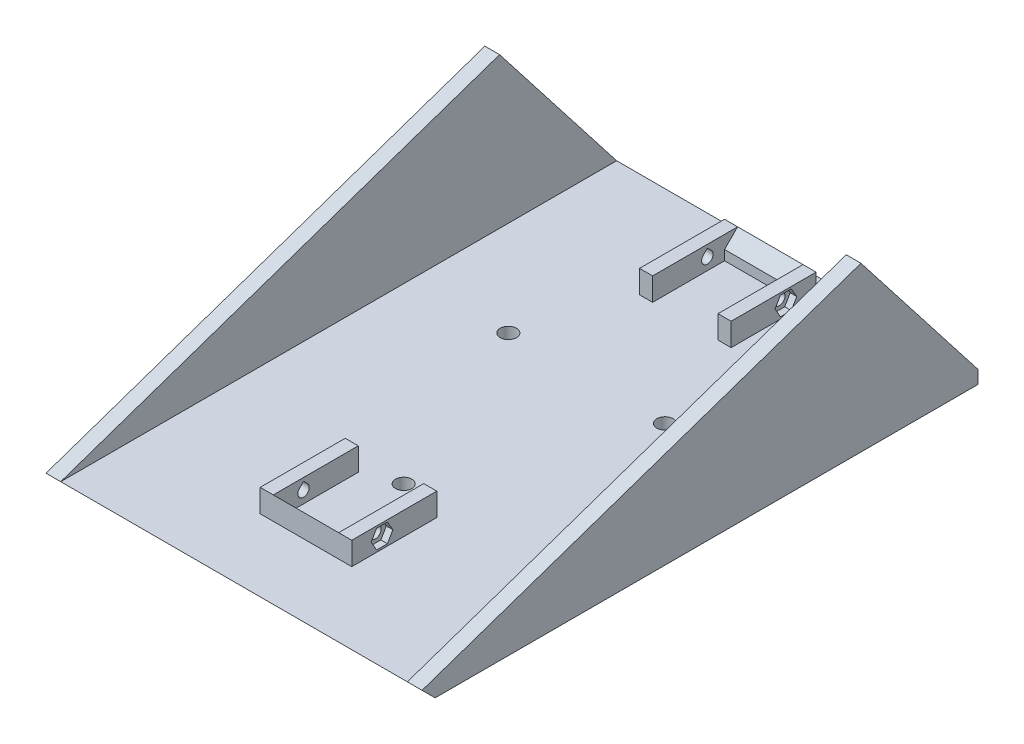
SolidWorks part; units mm, degrees
ref_plane "Front Plane" through (0, 0, 0) normal (0, 0, 1) x (1, 0, 0)
ref_plane "Top Plane" through (0, 0, 0) normal (0, 1, 0) x (1, 0, 0)
ref_plane "Right Plane" through (0, 0, 0) normal (1, 0, 0) x (0, 0, -1)
sketch "Sketch1" plane through (0, 0, 0) normal (0, 1, 0) x (1, 0, 0)
  line L1 (0, 0) -> (115, 0)
  line L2 (0, 0) -> (0, 170)
  line L3 (0, 170) -> (115, 170)
  line L4 (115, 0) -> (115, 170)
  line L5 (0, 170) -> (4.5, 170)
  line L6 (0, 170) -> (0, 0)
  line L7 (0, 0) -> (4.5, 0)
  line L8 (4.5, 170) -> (4.5, 0)
  dimension "D1" = 115
  dimension "D2" = 170
  dimension "D3" = 4.5
extrude "Boss-Extrude1" add sketch "Sketch1" along normal blind 4 contours L3 L8 L1 L4 | L8 L3 L2 L1 region at (2.25, 0, -85) region at (59.75, 0, -85)
extrude "Boss-Extrude2" add sketch "Sketch1<4>" along normal blind 50 contours L8 L3 L2 L1 region at (2.25, 0, -85)
sketch "Sketch1<4>" plane through (0, 0, 0) normal (0, 1, 0) x (1, 0, 0) same geometry as "Sketch1"
sketch "Sketch2" plane through (0, 0, 0) normal (-1, 0, 0) x (0, 0, 1)
  line L0 (-134.204, 50) -> (-170, 4)
  line L1 (0, 50) -> (-170, 50) construction
  line L2 (-170, 4) -> (-182.3926, 4)
  line L3 (-182.3926, 4) -> (-182.3926, 57.4026)
  line L4 (-182.3926, 57.4026) -> (5.7459, 57.4026)
  line L5 (5.7459, 57.4026) -> (5.7459, 4)
  line L6 (5.7459, 4) -> (0, 4)
  line L7 (0, 50) -> (0, 0) construction
  line L8 (0, 4) -> (-134.204, 50)
extrude "Cut-Extrude1" cut sketch "Sketch2" against normal up to surface (4.5 mm away) up to face at (4.5, 27, -85)
ref_axis "Axis1" through (57.5, 0, -170) along (0, 0, 1)
ref_plane "Plane1" through (57.5, 0, 0) normal (1, 0, 0) x (0, 0, -1)
mirror "Mirror1" about plane through (57.5, 0, 0) normal (1, 0, 0) of "Cut-Extrude1", "Boss-Extrude2"
sketch "Sketch3" plane through (0, 4, 0) normal (0, 1, 0) x (1, 0, 0)
  line L0 (4.5, 170) -> (110.5, 170) construction
  line L5 (57.5, 160) -> (47.5, 160)
  line L6 (47.5, 160) -> (47.5, 142)
  line L7 (57.5, 160) -> (57.5, 170) construction
  line L8 (4.5, 170) -> (110.5, 170) construction
  line L9 (110.5, 170) -> (110.5, 134.204) construction
  line L11 (57.5, 164) -> (43.5, 164)
  line L12 (43.5, 164) -> (43.5, 138)
  line L13 (43.5, 138) -> (47.5, 138)
  line L14 (57.5, 164) -> (57.5, 160)
  line L16 (47.5, 142) -> (47.5, 138)
  line L17 (43.5, 138) -> (57.5, 138) construction
  line L18 (47.5, 142) -> (57.5, 142) construction
  point P12 (57.5, 170)
  dimension "D1" = 10
  dimension "D2" = 106
  dimension "D3" = 10
  dimension "D5" = 26
  dimension "D4" = 4
extrude "Saliente-Extruir1" add sketch "Sketch3" along normal blind 7
sketch "Croquis1" plane through (0, 4, 0) normal (0, 1, 0) x (1, 0, 0)
  line L0 (47.5, 138) -> (47.5, 48) construction
  line L1 (47.5, 93) -> (18.6251, 93) construction
  line L2 (57.5, 26) -> (57.5, 22)
  line L3 (47.5, 26) -> (57.5, 26)
  line L4 (57.5, 22) -> (43.5, 22)
  line L5 (43.5, 22) -> (43.5, 48)
  line L6 (57.5, 160) -> (57.5, 164)
  line L7 (57.5, 164) -> (43.5, 164)
  line L8 (43.5, 164) -> (43.5, 138)
  line L9 (43.5, 138) -> (47.5, 138)
  line L10 (47.5, 138) -> (47.5, 160)
  line L11 (47.5, 160) -> (57.5, 160)
  line L12 (57.5, 160) -> (57.5, 164) construction
  line L13 (57.5, 164) -> (43.5, 164) construction
  line L14 (43.5, 164) -> (43.5, 138) construction
  line L15 (43.5, 138) -> (47.5, 138) construction
  line L16 (47.5, 138) -> (47.5, 160) construction
  line L17 (47.5, 160) -> (57.5, 160) construction
  line L18 (43.5, 48) -> (47.5, 48)
  line L19 (47.5, 48) -> (47.5, 26)
  dimension "D2" = 90
  dimension "D1" = 0
extrude "Saliente-Extruir2" add sketch "Croquis1" along normal blind 7
mirror "Simetría1" about plane through (57.5, 11, -164) normal (-1, 0, 0) of "Saliente-Extruir2", "Saliente-Extruir1"
sketch "Croquis2" plane through (47.5, 0, 0) normal (1, 0, 0) x (0, 0, -1)
  line L0 (48, 4) -> (138, 4) construction
  line L1 (93, 4) -> (93, 16.2134) construction
  line L2 (160, 7.5) -> (156.5, 7.5)
  line L3 (156.5, 7.5) -> (154.75, 7.5)
  line L4 (138, 4) -> (160, 4)
  line L5 (160, 4) -> (160, 11)
  line L6 (160, 11) -> (138, 11)
  line L7 (138, 11) -> (138, 4)
  line L8 (138, 4) -> (160, 4)
  line L9 (160, 4) -> (160, 11)
  line L10 (160, 11) -> (138, 11)
  line L11 (138, 11) -> (138, 4)
  line L12 (26, 4) -> (48, 4)
  line L13 (48, 4) -> (48, 11)
  line L14 (48, 11) -> (26, 11)
  line L15 (26, 11) -> (26, 4)
  line L16 (26, 4) -> (48, 4)
  line L17 (48, 4) -> (48, 11)
  line L18 (48, 11) -> (26, 11)
  line L19 (26, 11) -> (26, 4)
  line L20 (31.25, 9.9749) -> (32.4874, 8.7374)
  line L21 (154.75, 9.9749) -> (155.9874, 8.7374)
  line L22 (31.25, 9.9749) -> (30.0126, 8.7374)
  line L23 (154.75, 9.9749) -> (153.5126, 8.7374)
  arc A0 (153.5126, 8.7374) -> (155.9874, 8.7374) centre (154.75, 7.5) ccw
  arc A1 (32.4874, 8.7374) -> (30.0126, 8.7374) centre (31.25, 7.5) cw
  dimension "D3" = 3.5
  dimension "D4" = 1.75
  dimension "D1" = 0
  dimension "D2" = 0
extrude "Cortar-Extruir1" cut sketch "Croquis2" against normal blind 7 and the other way blind 31 contours A1 L20 L22 | A0 L21 L23 region at (47.5, 7.6229, -154.75) region at (47.5, 7.6229, -31.25)
sketch "Croquis4" plane through (71.5, 0, 0) normal (1, 0, 0) x (0, 0, -1)
  line L0 (154.75, 7.5) -> (154.75, 4) construction
  line L1 (158.0698, 7.5) -> (156.4099, 10.375)
  line L2 (156.4099, 10.375) -> (153.0901, 10.375)
  line L3 (153.0901, 10.375) -> (151.4302, 7.5)
  line L4 (151.4302, 7.5) -> (153.0901, 4.625)
  line L5 (153.0901, 4.625) -> (156.4099, 4.625)
  line L6 (156.4099, 4.625) -> (158.0698, 7.5)
  line L7 (164, 4) -> (138, 4) construction
  line L8 (48, 7.5) -> (138, 7.5) construction
  line L9 (48, 11) -> (48, 4) construction
  line L10 (138, 11) -> (138, 4) construction
  line L11 (93, 7.5) -> (93, 14.1152) construction
  line L18 (154.75, 7.5) -> (158.8346, 7.5) construction
  line L19 (29.5901, 4.625) -> (27.9302, 7.5)
  line L20 (32.9099, 4.625) -> (29.5901, 4.625)
  line L21 (34.5698, 7.5) -> (32.9099, 4.625)
  line L22 (32.9099, 10.375) -> (34.5698, 7.5)
  line L23 (29.5901, 10.375) -> (32.9099, 10.375)
  line L24 (27.9302, 7.5) -> (29.5901, 10.375)
  circle A0 centre (154.75, 7.5) radius 2.875 construction
  arc A1 (153.5126, 8.7374) -> (155.9874, 8.7374) centre (154.75, 7.5) ccw construction
  arc M13 (155.9874, 8.7374) -> (153.5126, 8.7374) centre (154.75, 7.5) cw
  line M14 (153.5126, 8.7374) -> (154.75, 9.9749)
  line M15 (154.75, 9.9749) -> (155.9874, 8.7374)
  dimension "D1" = 5.75
extrude "Cortar-Extruir2" cut sketch "Croquis4" against normal blind 2 contours L6 L1 L2 L3 L4 L5 M13 M14 M15 | L19 L24 L23 L22 L21 L20 region at (71.5, 6.1064, -157.1638)
chamfer "Chaflán1" distance 4 angle 45 1 edges at (57.5, 11, -26)
chamfer "Chaflán2" distance 4 angle 45 1 edges at (57.5, 11, -160)
sketch "Croquis5" plane through (0, 4, 0) normal (0, 1, 0) x (1, 0, 0)
  line L0 (57.5, 170) -> (57.5, 0) construction
  line L1 (4.5, 170) -> (110.5, 170) construction
  line L2 (4.5, 0) -> (110.5, 0) construction
  circle A0 centre (33.5457, 107.8308) radius 2.5
  circle A1 centre (57.5, 51.8662) radius 2.5
  circle A2 centre (81.4543, 107.8308) radius 2.5
extrude "Cortar-Extruir3" cut sketch "Croquis5" against normal blind 23.7
chamfer "Chaflán3" distance 4 angle 45 1 edges at (57.5, 0, 0)
